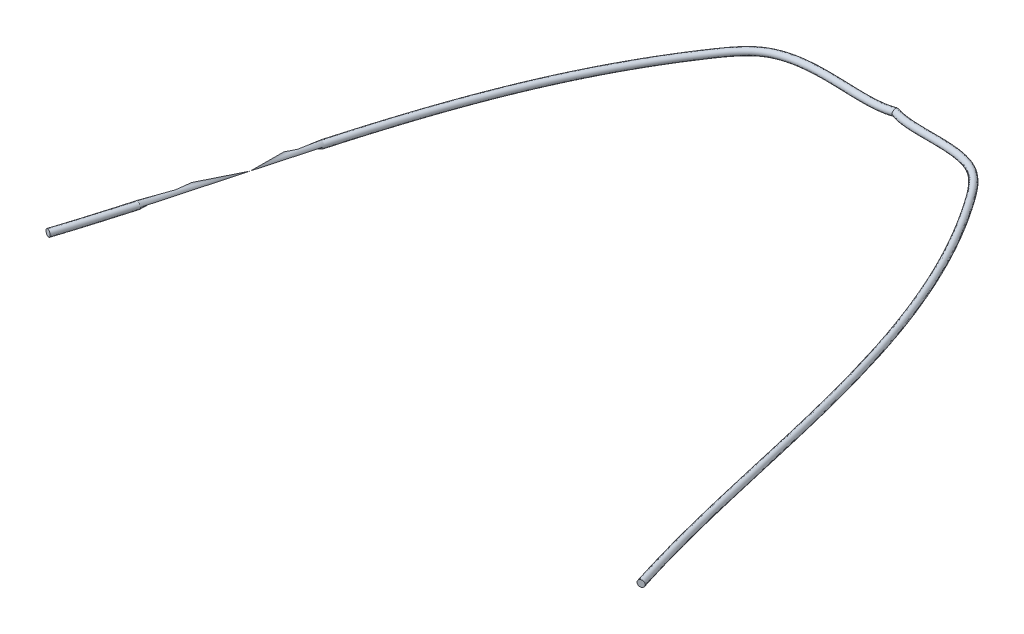
SolidWorks part; units mm, degrees
ref_plane "Front Plane" through (0, 0, 0) normal (0, 0, 1) x (1, 0, 0)
ref_plane "Top Plane" through (0, 0, 0) normal (0, 1, 0) x (1, 0, 0)
ref_plane "Right Plane" through (0, 0, 0) normal (1, 0, 0) x (0, 0, -1)
ref_plane "Plane1" through (0, 20.5189, 0) normal (0, 1, 0) x (1, 0, 0)
sketch "Sketch56" plane through (0, 20.5189, 0) normal (0, 1, 0) x (1, 0, 0)
  arc A2 (-15.6293, 16.1485) -> (-16.2695, 13.0158) centre (-6.278, 12.6057) ccw construction
  arc A3 (8.1975, 54.6974) -> (-0.6338, 48.7338) centre (8.5177, 44.7026) ccw construction
  spline S0 degree 3 poles (21.1429, 55.3021) (17.0052, 53.6872) (5.3653, 57.2666) (-15.4368, 28.4391) (-19.1921, 0.129) (-27.3147, -24.9182) knots 0 0 0 0 0.178647 0.230886 1 1 1 1
  point P2 (-16.0755, 14.6079)
  point P10 (3.0858, 53.0987)
  point P16 (-0.4704, 49.0861)
  point P18 (7.5776, 54.6583)
sketch "Sketch19" plane through (0, 20.5189, 0) normal (0, 1, 0) x (1, 0, 0)
  arc A2 (53.7305, 13.0158) -> (53.1636, 15.9824) centre (43.7374, 12.6437) ccw construction
  arc A3 (28.8375, 54.6974) -> (26.0834, 51.7075) centre (29.0834, 51.7075) ccw construction
  arc A4 (38.6757, 48.8215) -> (30.4819, 54.6974) centre (29.546, 44.7413) ccw construction
  spline S0 degree 3 poles (21.1429, 55.3021) (24.8443, 53.9946) (33.1651, 56.3282) (54.2916, 28.5963) (55.6895, -0.6904) (63.8226, -26.002) knots 0 0 0 0 0.134395 0.195672 1 1 1 1
  point P2 (34.0836, 10.0352)
  point P4 (63.2172, 16.4384)
  point P6 (54.3093, 14.8612)
  point P8 (0, 0)
  point P10 (53.5597, 14.5206)
  point P14 (40.5603, 50.4075)
  point P15 (30.46, 56.3659)
  point P16 (28.7198, 54.6854)
  point P24 (34.2992, 53.5395)
  point P28 (36.9903, 48.5186)
  point P29 (38.5089, 49.176)
sweep "Sweep2" add path "Sketch19" circular profile diameter 1 parameters "D3"=1
sweep "Sweep3" add path "Sketch56" circular profile diameter 1 parameters "D3"=1
